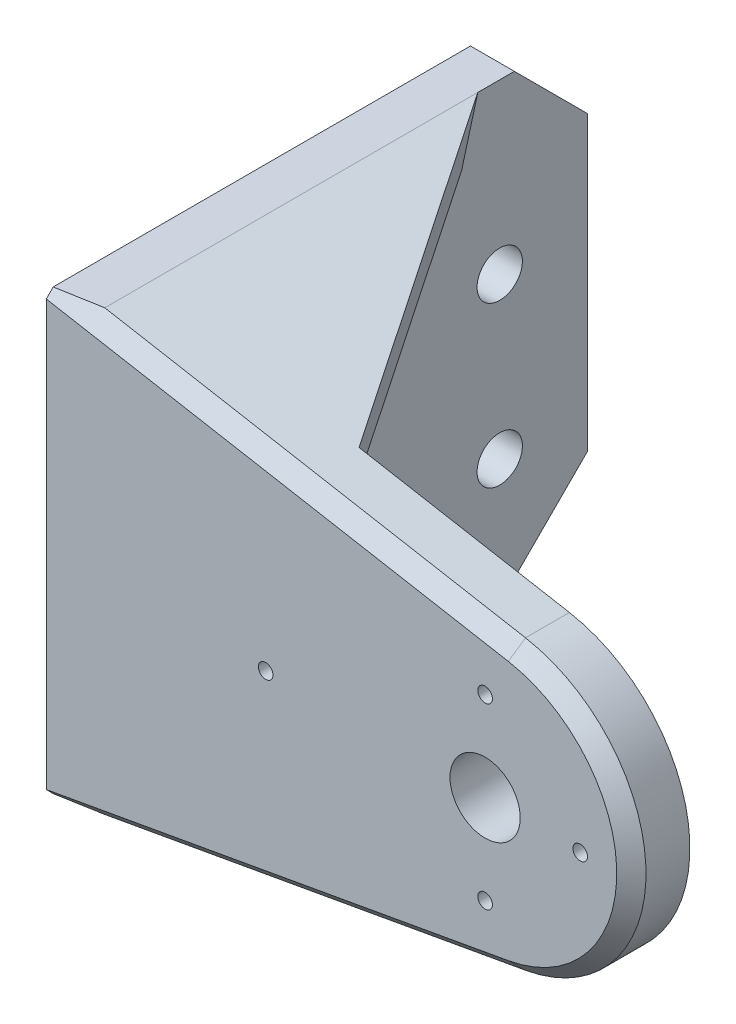
SolidWorks part; units mm, degrees
ref_plane "Front Plane" through (0, 0, 0) normal (0, 0, 1) x (1, 0, 0)
ref_plane "Top Plane" through (0, 0, 0) normal (0, 1, 0) x (1, 0, 0)
ref_plane "Right Plane" through (0, 0, 0) normal (1, 0, 0) x (0, 0, -1)
sketch "Sketch1" plane through (0, 0, 0) normal (0, 0, 1) x (1, 0, 0)
  line L0 (-24.444, 5.5562) -> (-24.444, -9.4438)
  line L1 (5.556, 5.5562) -> (-24.444, 5.5562) construction
  line L2 (-24.444, 5.5562) -> (-24.444, 20.5562)
  line L3 (-24.444, -9.4438) -> (-21.444, -9.4438)
  line L4 (-21.444, -9.4438) -> (7.3207, -4.2868)
  line L5 (-24.444, 20.5562) -> (-21.444, 20.5562)
  line L6 (-21.444, 20.5562) -> (7.3207, 15.3993)
  circle A1 centre (5.556, 5.5562) radius 1.984
  circle A2 centre (5.556, 5.5562) radius 10
  dimension "D1" = 20
  dimension "D2" = 30
  dimension "D3" = 15
  dimension "D4" = 15
  dimension "D5" = 3
  dimension "D6" = 3
extrude "Boss-Extrude1" add sketch "Sketch1" along normal blind 4 contours A2 L1 L0 L3 L4 | L1 A2 L6 L5 L2 | A1 A2 | A1 region at (-13.4785, -1.5234, 0) region at (-13.4785, 12.6359, 0) region at (5.556, 7.4841, 0) region at (-0.6794, 13.009, 0)
sketch "Sketch2" plane through (0, 0, 4) normal (0, 0, 1) x (1, 0, 0)
  circle A0 centre (5.556, 5.5562) radius 1.984 construction
  circle A1 centre (5.556, 5.5562) radius 1.984
  circle A2 centre (5.556, 5.5562) radius 1.05
  dimension "D1" = 2.1
sketch "Sketch3" plane through (0, 0, 0) normal (0, 0, -1) x (-1, 0, 0)
  line L0 (21.444, 20.5562) -> (21.444, -9.4438)
  line L1 (21.444, -9.4438) -> (24.444, -9.4438)
  line L2 (24.444, -9.4438) -> (24.444, 20.5562)
  line L3 (24.444, 20.5562) -> (21.444, 20.5562)
extrude "Boss-Extrude2" add sketch "Sketch3" along normal blind 30
sketch "Sketch4" plane through (2.9028, 16.1914, 0) normal (0.1765, 0.9843, 0) x (0.9843, -0.1765, 0)
  line L0 (-24.735, 22.5) -> (-10.1233, 0)
  line L1 (-24.735, 0) -> (4.4883, 0) construction
  line L3 (-24.735, 15) -> (-24.735, 30) construction
  line L4 (-24.735, 30) -> (-24.735, 0) construction
  line L5 (-10.1233, 0) -> (-10.1233, -0.5)
  line L6 (-10.1233, -0.5) -> (-24.735, -0.5)
  line L7 (-24.735, -4) -> (-24.735, 0) construction
  line L8 (-24.735, -0.5) -> (-24.735, 22.5)
  dimension "D1" = 0.5
extrude "Boss-Extrude3" add sketch "Sketch4" against normal blind 4
ref_axis "Axis1" through (5.556, 5.5562, 0) along (-1, 0, 0)
ref_plane "Plane1" through (0, 5.5562, 0) normal (0, 1, 0) x (-1, 0, 0)
chamfer "Chamfer1" distance 5 angle 45 1 edges at (-21.444, 3.5244, 0)
chamfer "Chamfer2" distance 5 angle 45 2 edges at (-22.944, -9.4438, -30) (-22.944, 20.5562, -30)
chamfer "Chamfer3" distance 1 angle 45 3 edges at (-7.0617, -6.8653, 4) (15.556, 5.5562, 4) (-7.0617, 17.9778, 4)
sketch "Sketch6" plane through (-21.444, 0, 0) normal (1, 0, 0) x (0, 0, -1)
  line L0 (30, 9.0472) -> (9.61, 9.0472) construction
  line L1 (30, 15.5562) -> (30, -4.4438) construction
  line L2 (30, -1.8898) -> (9.5502, -1.8898) construction
  line L3 (24, 9.0472) -> (24, -1.8898) construction
  line L4 (11, 9.0472) -> (11, -1.8898) construction
  circle A0 centre (11, 9.0472) radius 1.55
  circle A1 centre (24, 9.0472) radius 1.55
  circle A2 centre (11, -1.8898) radius 1.55
  circle A3 centre (24, -1.8898) radius 1.55
  dimension "D1" = 3.1
  dimension "D2" = 3.1
  dimension "D3" = 3.1
  dimension "D4" = 3.1
  dimension "D5" = 6
  dimension "D6" = 13
extrude "Cut-Extrude3" cut sketch "Sketch6" against normal up to next
sketch "Sketch7" plane through (0, 0, 0) normal (0, 0, -1) x (-1, 0, 0)
  circle A0 centre (-5.556, 5.5562) radius 1.05 construction
  circle A1 centre (-5.556, 5.5562) radius 1.05
  circle A2 centre (-5.556, 5.5562) radius 2.4
  dimension "D1" = 4.8
ref_point "Point1"
extrude "Cut-Extrude4" cut sketch "Sketch7" against normal up to next contours A2
sketch "Sketch8" plane through (0, 0, 0) normal (0, 0, -1) x (-1, 0, 0)
  circle A0 centre (9.444, 5.5563) radius 0.5 construction
  circle A1 centre (-5.556, 11.6563) radius 0.5 construction
  circle A2 centre (-5.556, -0.5437) radius 0.5 construction
  circle A3 centre (-12.056, 5.5563) radius 0.5 construction
  circle A4 centre (9.444, 5.5563) radius 0.5
  circle A5 centre (-5.556, 11.6563) radius 0.5
  circle A6 centre (-5.556, -0.5437) radius 0.5
  circle A7 centre (-12.056, 5.5563) radius 0.5
extrude "Cut-Extrude5" cut sketch "Sketch8" against normal up to next
